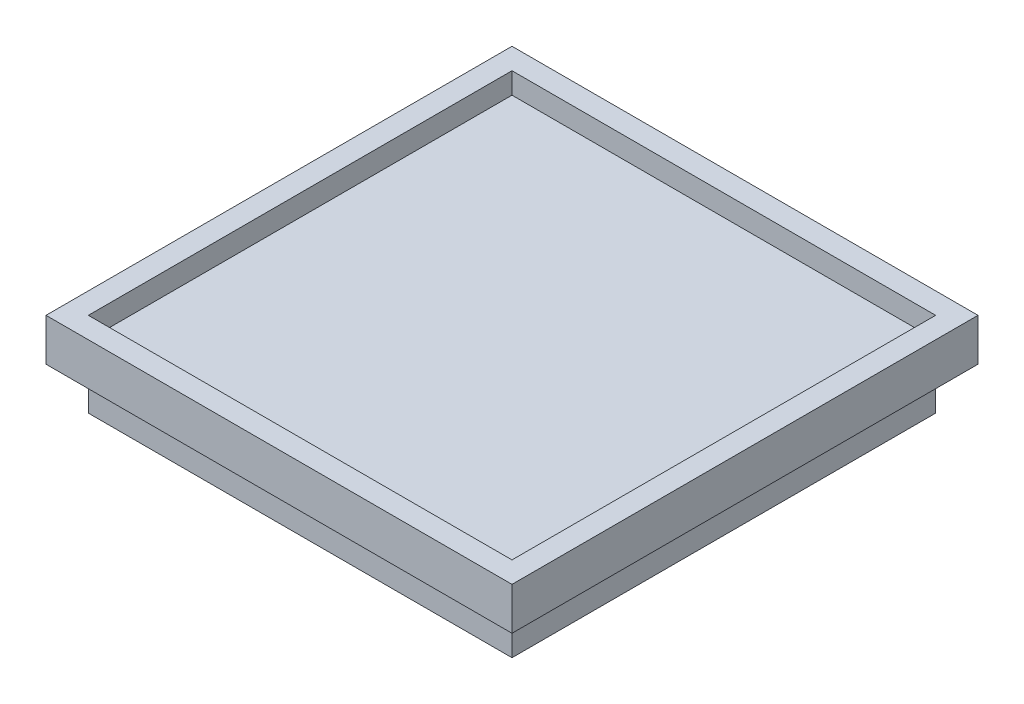
SolidWorks part; units mm, degrees
ref_plane "Front Plane" through (0, 0, 0) normal (0, 0, 1) x (1, 0, 0)
ref_plane "Top Plane" through (0, 0, 0) normal (0, 1, 0) x (1, 0, 0)
ref_plane "Right Plane" through (0, 0, 0) normal (1, 0, 0) x (0, 0, -1)
sketch "Sketch1" plane through (0, 0, 0) normal (0, 1, 0) x (1, 0, 0)
  line L1 (-69.85, -69.85) -> (69.85, -69.85)
  line L2 (-69.85, -69.85) -> (-69.85, 69.85)
  line L3 (-69.85, 69.85) -> (69.85, 69.85)
  line L4 (69.85, -69.85) -> (69.85, 69.85)
  line L5 (-69.85, -69.85) -> (69.85, 69.85) construction
  line L6 (-69.85, 69.85) -> (69.85, -69.85) construction
  point P0 (0, 0)
extrude "Boss-Extrude1" add sketch "Sketch1" along normal blind 6.35
sketch "Sketch4" plane through (0, 6.35, 0) normal (0, 1, 0) x (1, 0, 0)
  line L1 (-69.85, -69.85) -> (69.85, -69.85)
  line L2 (-69.85, -69.85) -> (-69.85, 69.85)
  line L3 (-69.85, 69.85) -> (69.85, 69.85)
  line L4 (69.85, -69.85) -> (69.85, 69.85)
  line L5 (-69.85, -69.85) -> (69.85, 69.85) construction
  line L6 (-69.85, 69.85) -> (69.85, -69.85) construction
  point P0 (0, 0)
extrude "Boss-Extrude2" add sketch "Sketch4" along normal blind 6.35
shell "Shell1" thickness 6.35 removed face at (0, 12.7, 0)
sketch "Sketch5" plane through (0, 0, 0) normal (0, -1, 0) x (-1, 0, 0)
  line L1 (63.5, 63.5) -> (-63.5, 63.5)
  line L2 (63.5, 63.5) -> (63.5, -63.5)
  line L3 (63.5, -63.5) -> (-63.5, -63.5)
  line L4 (-63.5, 63.5) -> (-63.5, -63.5)
  line L5 (63.5, 63.5) -> (-63.5, -63.5) construction
  line L6 (63.5, -63.5) -> (-63.5, 63.5) construction
  point P0 (0, 0)
  dimension "D1" = 127
  dimension "D2" = 127
extrude "Boss-Extrude4" add sketch "Sketch5" along normal blind 12.7 contours L3 L4 L1 L2
shell "Shell2" thickness 6.35 removed face at (0, -12.7, 0)
